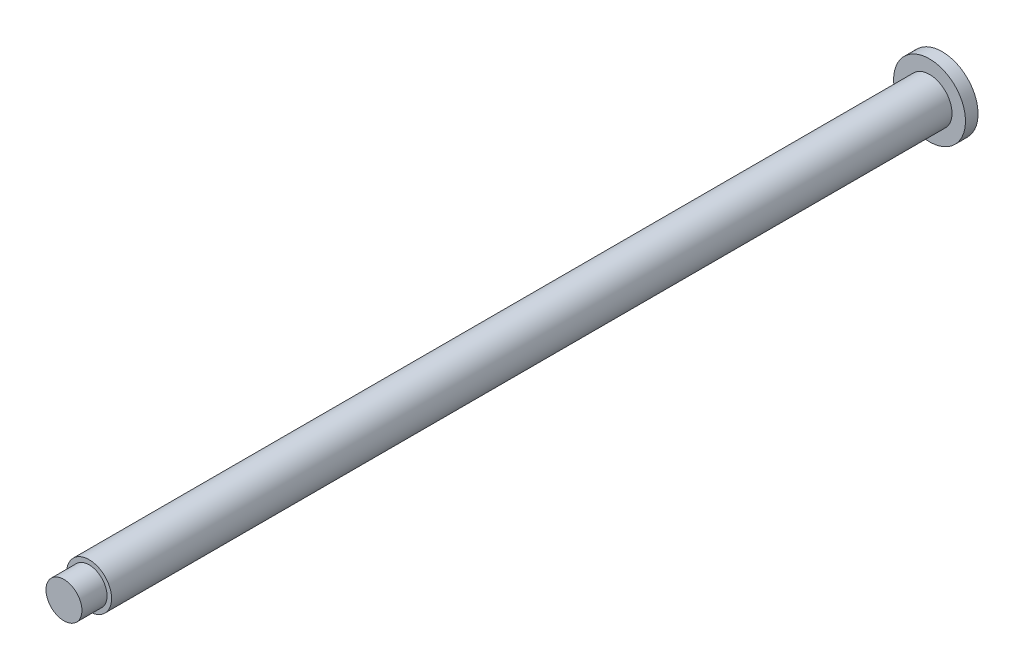
SolidWorks part; units mm, degrees
ref_plane "Front Plane" through (0, 0, 0) normal (1, 0, 0) x (0, 1, 0)
ref_plane "Top Plane" through (0, 0, 0) normal (0, 0, 1) x (0, 1, 0)
ref_plane "Right Plane" through (0, 0, 0) normal (0, 1, 0) x (-1, 0, 0)
sketch "Sketch1" plane through (0, 0, 0) normal (0, 0, 1) x (0, 1, 0)
  circle A0 centre (0, 0) radius 2.5
  dimension "D1" = 5
extrude "Boss-Extrude1" add sketch "Sketch1" along normal blind 93.5 contours A0
sketch "Sketch2" plane through (0, 0, 0) normal (0, 0, -1) x (1, 0, 0)
  circle A0 centre (0, 0) radius 4
  dimension "D1" = 8
extrude "Boss-Extrude2" add sketch "Sketch2" along normal blind 1.4
sketch "Sketch3" plane through (0, 0, -1.4) normal (0, 0, -1) x (1, 0, 0)
  circle A0 centre (0, 0) radius 2.05
  dimension "D1" = 4.1
extrude "Cut-Extrude1" cut sketch "Sketch3" against normal blind 3
sketch "Sketch4" plane through (0, 0, 93.5) normal (0, 0, 1) x (1, 0, 0)
  circle A0 centre (0, 0) radius 2
extrude "Boss-Extrude3" add sketch "Sketch4" along normal blind 2.8
equation "\"whitekey_cutout_length\"= 101.5"
equation "\"key_mount_recess_length\"=50"
equation "\"key_mount_recess_height\"=12.5"
equation "\"key_mount_recess_depth\"=1.5"
equation "\"wall_thickness\"=10"
equation "\"guide_brace_height\"=20"
equation "\"guide_brace_thickness\"=2"
equation "\"dowel_recess_depth\"=9"
equation "\"dowel_recess_offset\"=3.25"
equation "\"base_mount_height\"=40"
equation "\"base_rear_length\"=80"
equation "\"base_front_length\"=111.5"
equation "\"screw_hole_wall_offset\"=7.25"
equation "\"screw_hole_edge_inset\"=4.5"
equation "\"screw_hole_diameter\"=3.8"
equation "\"screw_head_hole_diameter\"=6.7"
equation "\"screw_nut_hole_side_len\"=3.5"
equation "\"screw_nut_recess_offset\"=0.4"
equation "\"screw_head_and_nut_recess_depth\"=2.5"
equation "\"screw_shaft_diameter\"=3.5"
equation "\"switch_board_width\"=30"
equation "\"switch_board_wall_offset\"=11.5"
equation "\"heatset_insert_hole_diameter\"=4.8"
equation "\"heatset_insert_hole_depth\"=3.8"
equation "\"front_rear_panel_width\"=23.75"
equation "\"rod_length_adj\"=0.5"
equation "\"rod_insert_length\"=2.8"
equation "\"D1@Boss-Extrude3\"=\"rod_insert_length\""
equation "\"D1@Boss-Extrude2\"=2-\"rod_length_adj\"-0.1"
equation "\"D1@Boss-Extrude1\"=\"rod_length_adj\"+93.00mm"
equation "\"switch_board_thickness\"=1.6"
equation "\"rod_diameter\"=5"
equation "\"rod_head_diameter\"=8"
equation "\"switch_black_key_mount_height\"=8"
equation "\"switch_white_key_mount_height\"=3"
equation "\"D1@Sketch1\"=\"rod_diameter\""
equation "\"D1@Sketch2\"=\"rod_head_diameter\""
equation "\"D1@Sketch3\"=\"rod_diameter\"-1+0.1"
equation "\"D1@Sketch4\"=\"rod_diameter\"-1"
